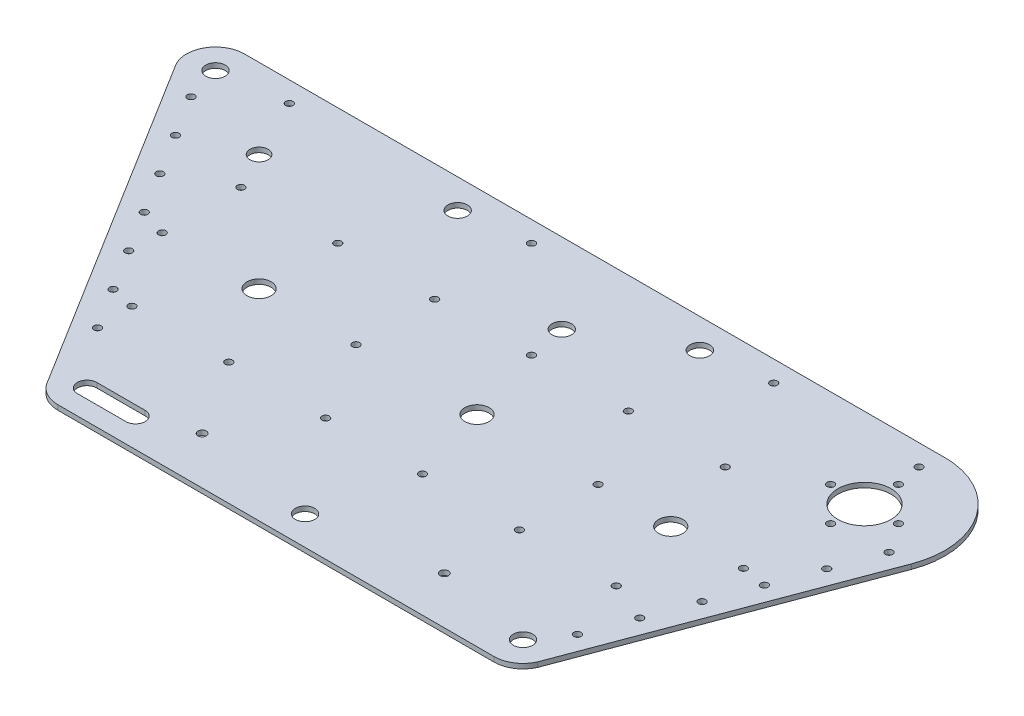
SolidWorks part; units mm, degrees
ref_plane "Front Plane" through (0, 0, 0) normal (0, 0, 1) x (1, 0, 0)
ref_plane "Top Plane" through (0, 0, 0) normal (0, 1, 0) x (1, 0, 0)
ref_plane "Right Plane" through (0, 0, 0) normal (1, 0, 0) x (0, 0, -1)
sketch "Sketch2" plane through (0, 0, 0) normal (0, 1, 0) x (1, 0, 0)
  line L0 (-106.005, 144.9436) -> (182.9628, 145.1972)
  line L1 (160.9924, -19) -> (-18.9986, -19)
  line L2 (171.9007, -12) -> (214.0696, 100.3323)
  line L3 (-18.9986, -3) -> (1.0004, -3)
  line L4 (1.0003, -11) -> (-18.9986, -11)
  line L5 (-29.6999, -12.4286) -> (-116.0853, 126.6112)
  circle A0 centre (182.992, 112) radius 11
  circle A1 centre (-18.9988, 64) radius 5
  circle A2 centre (70.9964, 64) radius 5
  circle A3 centre (150.9927, 64) radius 5
  circle A4 centre (-78.996, 136.5) radius 1.5
  circle A5 centre (20.9989, 136.5) radius 1.5
  circle A6 centre (120.9939, 136.5) radius 1.5
  circle A7 centre (180.9909, 136.5) radius 1.5
  circle A8 centre (170.3325, 6.1186) radius 1.5
  circle A9 centre (177.3307, 24.8545) radius 1.5
  circle A10 centre (184.3286, 43.5896) radius 1.5
  circle A11 centre (191.3265, 62.3248) radius 1.5
  circle A12 centre (198.3244, 81.0602) radius 1.5
  circle A13 centre (-38.3619, 16.6713) radius 1.5
  circle A14 centre (-48.9163, 33.6588) radius 1.5
  circle A15 centre (-59.4708, 50.6466) radius 1.5
  circle A16 centre (-70.0255, 67.6347) radius 1.5
  circle A17 centre (-80.5803, 84.623) radius 1.5
  circle A18 centre (70.9966, -7) radius 4
  circle A19 centre (120.9939, 0.5) radius 1.75
  circle A20 centre (20.9989, 0.5) radius 1.75
  ellipse E0 centre (-105.9945, 133) end of major axis (-105.9945, 137) minor radius 4
  ellipse E1 centre (160.9926, -7) end of major axis (160.9926, -3) minor radius 4
  ellipse E2 centre (-18.9986, -7) end of major axis (-18.9986, -11) minor radius 4 (-18.9986, -3) -> (-18.9986, -11) ccw
  ellipse E3 centre (182.992, 112) end of major axis (182.992, 123) minor radius 11
  ellipse E4 centre (-105.9945, 133) end of major axis (-105.9945, 144.9436) minor radius 11.943 (-106.005, 144.9436) -> (-116.0853, 126.6112) ccw
  ellipse E5 centre (182.992, 112) end of major axis (182.992, 145.1972) minor radius 33.1955 (214.0696, 100.3323) -> (182.9628, 145.1972) ccw
  ellipse E6 centre (1.0003, -7) end of major axis (1.0004, -3) minor radius 4 (1.0003, -11) -> (1.0004, -3) ccw
  ellipse E7 centre (182.9908, 126) end of major axis (182.9908, 127.5) minor radius 1.4999
  ellipse E8 centre (196.9901, 112) end of major axis (196.9901, 113.5) minor radius 1.4999
  ellipse E9 centre (168.9915, 112) end of major axis (168.9915, 113.5) minor radius 1.4999
  ellipse E10 centre (182.9908, 98) end of major axis (182.9908, 99.5) minor radius 1.4999
  ellipse E11 centre (-18.9986, -7) end of major axis (-18.9986, -19) minor radius 11.9993 (-29.6999, -12.4286) -> (-18.9986, -19) ccw
  ellipse E12 centre (160.9926, -7) end of major axis (160.9926, 5) minor radius 11.9994 (160.9924, -19) -> (171.9007, -12) ccw
  ellipse E15 centre (120.9939, 64) end of major axis (120.994, 65.5) minor radius 1.4999
  ellipse E16 centre (20.9989, 64) end of major axis (20.9989, 65.5) minor radius 1.4999
  ellipse E17 centre (-58.997, 64) end of major axis (-58.997, 65.5) minor radius 1.4999
  ellipse E18 centre (180.9909, 64) end of major axis (180.9909, 65.5) minor radius 1.4999
  ellipse E22 centre (60.9969, 96.5) end of major axis (60.9969, 98) minor radius 1.4999
  ellipse E23 centre (140.9929, 96.5) end of major axis (140.9929, 98) minor radius 1.4999
  ellipse E24 centre (160.992, 31.5) end of major axis (160.992, 33) minor radius 1.4999
  ellipse E25 centre (80.996, 31.5) end of major axis (80.996, 33) minor radius 1.4999
  ellipse E26 centre (-18.9991, 96.5) end of major axis (-18.9991, 98) minor radius 1.4999
  ellipse E27 centre (-38.998, 31.5) end of major axis (-38.998, 33) minor radius 1.4999
  ellipse E31 centre (-101.6892, 118.5984) end of major axis (-101.6892, 120.0984) minor radius 1.4999
  ellipse E32 centre (-91.1347, 101.6106) end of major axis (-91.1347, 103.1106) minor radius 1.4999
  ellipse E38 centre (205.3225, 99.7958) end of major axis (205.3225, 101.2958) minor radius 1.4999
  ellipse E45 centre (20.9989, 96.5) end of major axis (20.9989, 98) minor radius 1.4999
  ellipse E46 centre (100.995, 96.5) end of major axis (100.995, 98) minor radius 1.4999
  ellipse E47 centre (-58.9971, 96.5) end of major axis (-58.997, 98) minor radius 1.4999
  ellipse E48 centre (0.9999, 31.5) end of major axis (1, 33) minor radius 1.4999
  ellipse E49 centre (40.9979, 31.5) end of major axis (40.9979, 33) minor radius 1.4999
  ellipse E50 centre (120.9939, 31.5) end of major axis (120.994, 33) minor radius 1.4999
  ellipse E51 centre (-66.9967, 112) end of major axis (-66.9966, 115.75) minor radius 3.7498
  ellipse E52 centre (57.9973, 112) end of major axis (53.9973, 112) minor radius 4
  ellipse E53 centre (-5.9995, 133) end of major axis (-5.9995, 137) minor radius 4
  ellipse E54 centre (93.9954, 133) end of major axis (93.9954, 137) minor radius 4
  dimension "D1" = 22
  dimension "D2" = 10
  dimension "D3" = 10
  dimension "D4" = 10
  dimension "D5" = 3
  dimension "D6" = 3
  dimension "D7" = 3
  dimension "D8" = 3
  dimension "D9" = 3
  dimension "D10" = 3
  dimension "D11" = 3
  dimension "D12" = 3
  dimension "D13" = 3
  dimension "D14" = 3
  dimension "D15" = 3
  dimension "D16" = 3
  dimension "D17" = 3
  dimension "D18" = 3
  dimension "D19" = 8
  dimension "D20" = 3.5
extrude "Boss-Extrude1" add sketch "Sketch2" along normal blind 2 contours L1 E12 L2 E5 L0 E4 L5 E11 E54 E53 E52 E51 E50 E49 E48 E47 E46 E45 E38 region at (58.7758, 0, -70.1598)
